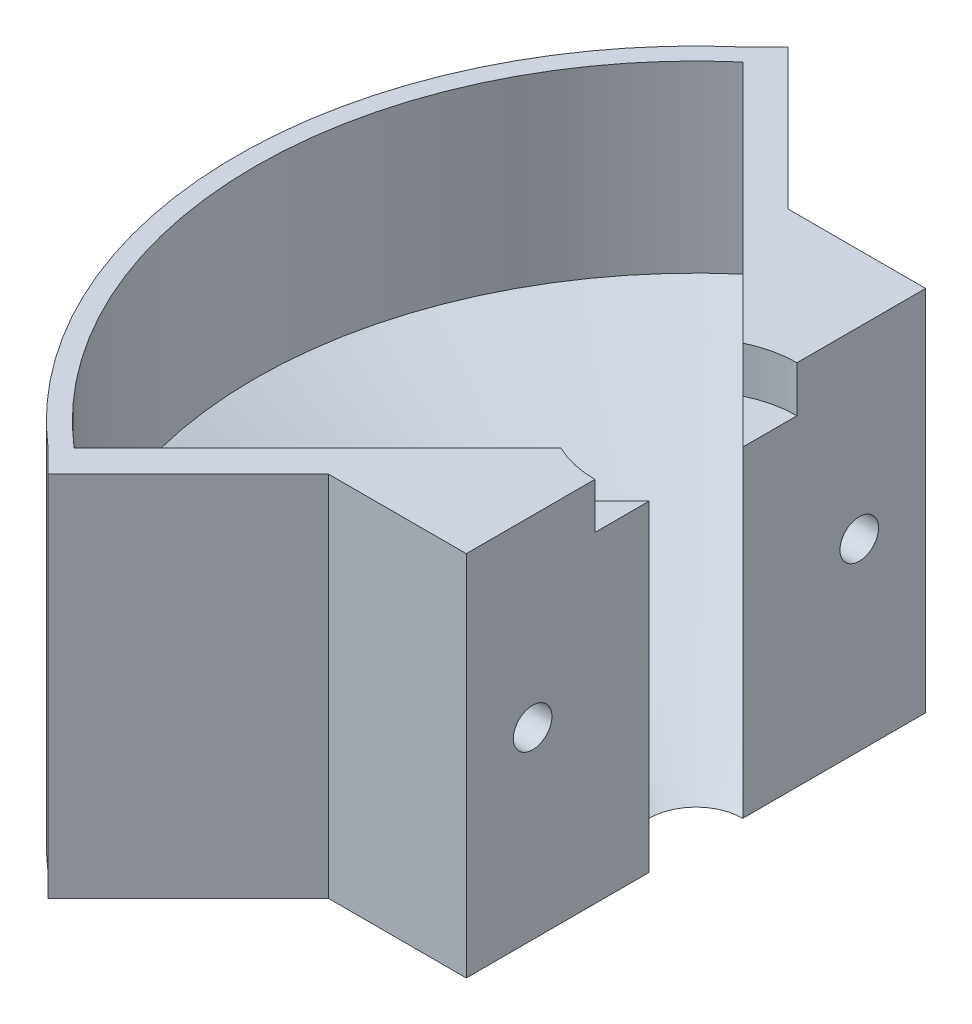
SolidWorks part; units mm, degrees
note: The reader was unsure of these and kept them because the rebuilt part matched: shared geometry of "Sketch4<3>".
ref_plane "Front Plane" through (0, 0, 0) normal (0, 0, 1) x (1, 0, 0)
ref_plane "Top Plane" through (0, 0, 0) normal (0, 1, 0) x (1, 0, 0)
ref_plane "Right Plane" through (0, 0, 0) normal (1, 0, 0) x (0, 0, -1)
sketch "Sketch1" plane through (0, 0, 0) normal (0, 0, 1) x (1, 0, 0)
  line L0 (0, 0) -> (0, 44.4235) construction
  line L1 (0, 0) -> (-6.477, 0)
  line L2 (-6.477, 0) -> (-60.96, 25.4058)
  line L3 (-60.96, 25.4058) -> (-60.96, 50.8)
  line L4 (-60.96, 50.8) -> (-63.5, 50.8)
  line L5 (-63.5, 50.8) -> (-63.5, 0)
  line L6 (-63.5, 0) -> (-6.477, 0)
  dimension "D1" = 6.477
  dimension "D2" = 63.5
  dimension "D3" = 2.54
  dimension "D4" = 25
  dimension "D5" = 50.8
revolve "Revolve1" add sketch "Sketch1" angle 90 about L0
sketch "Sketch4" plane through (0, 0, 0) normal (0, -1, 0) x (-1, 0, 0)
  line L0 (0, 31.75) -> (0, -31.75)
  line L1 (19.05, -31.75) -> (-19.05, -31.75)
  line L2 (19.05, -31.75) -> (19.05, 31.75)
  line L3 (19.05, 31.75) -> (-19.05, 31.75)
  line L4 (-19.05, -31.75) -> (-19.05, 31.75)
  line L5 (19.05, -31.75) -> (-19.05, 31.75) construction
  line L6 (19.05, 31.75) -> (-19.05, -31.75) construction
  line L7 (0, 6.477) -> (41.5458, 48.0228)
  line L8 (0, -6.477) -> (41.5458, -48.0228)
  line L9 (-0.587, -0.9783) -> (0, 0) construction
  line L10 (0, 0) -> (63.5, 0) construction
  line L13 (0, -6.477) -> (0, -63.5)
  line L14 (0, 63.5) -> (0, 6.477)
  line L15 (0, -6.477) -> (0, -63.5)
  line L16 (0, 63.5) -> (0, 6.477)
  circle A0 centre (0, 0) radius 6.477
  arc A1 (0, -63.5) -> (0, 63.5) centre (0, 0) ccw construction
  arc A4 (0, -6.477) -> (0, 6.477) centre (0, 0) ccw
  arc A5 (0, -63.5) -> (0, 63.5) centre (0, 0) ccw
  arc A6 (0, -6.477) -> (0, 6.477) centre (0, 0) ccw
  arc A7 (0, -63.5) -> (0, 63.5) centre (0, 0) ccw
  arc M7 (0, -63.5) -> (0, 63.5) centre (0, 0) ccw
  line M11 (0, -6.477) -> (0, -63.5)
  line M12 (0, 63.5) -> (0, 6.477)
  dimension "D1" = 38.1
  dimension "D2" = 63.5
  dimension "D3" = 45
  dimension "D4" = 45
  dimension "D5" = 0
extrude "Boss-Extrude3" add sketch "Sketch4" against normal blind 50.8 contours L7 L2 L3 M12 | L8 L1 L2 M11
extrude "Cut-Extrude1" cut sketch "Sketch4<3>" against normal up to next contours L2 L7 L3 M7 M12 | L8 L2 L1 M11 M7
sketch "Sketch4<3>" plane through (0, 0, 0) normal (0, -1, 0) x (-1, 0, 0) same geometry as "Sketch4"
sketch "Sketch5" plane through (0, 0, 0) normal (0, -1, 0) x (1, 0, 0)
  line L0 (-19.05, 31.75) -> (-38.4343, 51.1343)
  line L1 (-41.5458, 48.0228) -> (-38.4343, 51.1343)
  line L2 (0, 0) -> (-63.5, 0) construction
  line L3 (-19.05, -31.75) -> (-19.05, -25.527)
  line L4 (-19.05, -31.75) -> (-38.4343, -51.1343)
  line L5 (-41.5458, -48.0228) -> (-38.4343, -51.1343)
  line L6 (-19.05, -25.527) -> (-41.5458, -48.0228)
  line L8 (-19.05, 25.527) -> (-41.5458, 48.0228)
  line L9 (-41.5458, -48.0228) -> (-19.05, -25.527)
  line L10 (-19.05, -25.527) -> (-19.05, -31.75)
  line L11 (-19.05, -31.75) -> (0, -31.75)
  line L12 (0, -31.75) -> (0, -6.477)
  line L13 (0, 6.477) -> (0, 31.75)
  line L14 (0, 31.75) -> (-19.05, 31.75)
  line L15 (-19.05, 31.75) -> (-19.05, 25.527)
  line L16 (-19.05, 25.527) -> (-41.5458, 48.0228)
  line L17 (-41.5458, -48.0228) -> (-19.05, -25.527)
  line L18 (-19.05, -25.527) -> (-19.05, -31.75)
  line L19 (-19.05, -31.75) -> (0, -31.75)
  line L20 (0, -31.75) -> (0, -6.477)
  line L21 (0, 6.477) -> (0, 31.75)
  line L22 (0, 31.75) -> (-19.05, 31.75)
  line L23 (-19.05, 31.75) -> (-19.05, 25.527)
  arc A2 (-41.5458, 48.0228) -> (-41.5458, -48.0228) centre (0, 0) ccw
  arc A3 (0, 6.477) -> (0, -6.477) centre (0, 0) ccw
  arc A4 (-41.5458, 48.0228) -> (-41.5458, -48.0228) centre (0, 0) ccw
  arc A5 (0, 6.477) -> (0, -6.477) centre (0, 0) ccw
  line M14 (-19.05, 25.527) -> (-41.5458, 48.0228)
  line M16 (-41.5458, -48.0228) -> (-19.05, -25.527)
  line M17 (-19.05, -25.527) -> (-19.05, -31.75)
  line M23 (-19.05, 31.75) -> (-19.05, 25.527)
  dimension "D1" = 0
extrude "Boss-Extrude4" add sketch "Sketch5" against normal blind 50.8 contours L1 L0 M14 M23 | L5 L4 M16 M17
sketch "Sketch6" plane through (0, 50.8, 0) normal (0, 1, 0) x (1, 0, 0)
  circle A0 centre (0, 0) radius 13.97
  dimension "D1" = 27.94
extrude "Cut-Extrude2" cut sketch "Sketch6" against normal blind 6.35
sketch "Sketch7" plane through (0, 0, 0) normal (1, 0, 0) x (0, 0, -1)
  circle A0 centre (-22.575, 25.4) radius 2.665 construction
  circle A1 centre (22.575, 25.4) radius 2.665 construction
  circle A2 centre (-22.575, 25.4) radius 2.665
  circle A3 centre (22.575, 25.4) radius 2.665
extrude "Cut-Extrude3" cut sketch "Sketch7" against normal blind 8.89
